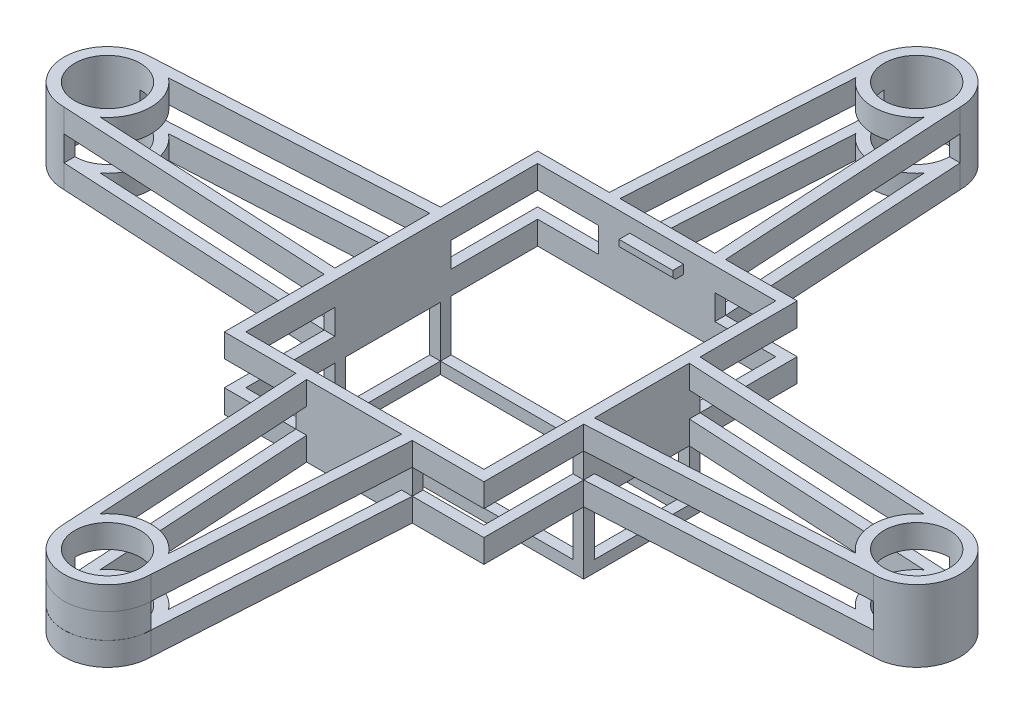
SolidWorks part; units mm, degrees
ref_plane "Front Plane" through (0, 0, 0) normal (0, 0, 1) x (1, 0, 0)
ref_plane "Top Plane" through (0, 0, 0) normal (0, 1, 0) x (1, 0, 0)
ref_plane "Right Plane" through (0, 0, 0) normal (1, 0, 0) x (0, 0, -1)
other "Center of Mass"
sketch "Sketch1" plane through (0, 0, 0) normal (0, 1, 0) x (1, 0, 0)
  line L0 (-15.0219, 23.4518) -> (-15.0219, 12.6018)
  line L1 (-13.8219, 22.2518) -> (12.7781, 22.2518)
  line L2 (-13.8219, 22.2518) -> (-13.8219, -10.3482)
  line L3 (-13.8219, -10.3482) -> (12.7781, -10.3482)
  line L4 (12.7781, 22.2518) -> (12.7781, -10.3482)
  line L5 (-15.0219, -11.5482) -> (-7.0219, -11.5482)
  line L6 (13.9781, 23.4518) -> (13.9781, 12.6018)
  line L7 (-15.0219, 23.4518) -> (-7.0219, 23.4518)
  line L8 (-0.5219, 23.4518) -> (-0.5219, 46.4518) construction
  line L9 (-5.3719, 51.3018) -> (-7.0219, 23.4518)
  line L10 (4.3281, 51.3018) -> (5.9781, 23.4518)
  line L11 (-4.3465, 48.3194) -> (-5.824, 23.3808)
  line L12 (3.3027, 48.3194) -> (4.7802, 23.3808)
  line L13 (-15.0219, 6.1018) -> (-40.8719, 6.1018) construction
  line L14 (4.3373, -39.0982) -> (5.9781, -11.5482)
  line L15 (3.31, -36.1101) -> (4.776, -11.5482)
  line L16 (-5.3719, -39.3982) -> (-7.0219, -11.5482)
  line L17 (-4.3538, -36.1101) -> (-5.8198, -11.5482)
  line L18 (-5.8198, 23.4518) -> (4.776, 23.4518)
  line L19 (-15.0219, 23.4518) -> (13.9781, 23.4518) construction
  line L20 (5.9781, 23.4518) -> (13.9781, 23.4518)
  line L21 (3.1302, 51.2308) -> (4.7802, 23.3808) construction
  line L22 (-4.174, 51.2308) -> (-5.824, 23.3808) construction
  line L23 (5.9781, -11.5482) -> (13.9781, -11.5482)
  line L24 (-15.0219, -11.5482) -> (13.9781, -11.5482) construction
  line L25 (-5.8198, -11.5482) -> (4.776, -11.5482)
  line L26 (-15.0219, 12.6018) -> (-45.7219, 10.9518)
  line L27 (-15.0219, -0.3982) -> (-45.7219, 1.2518)
  line L28 (-15.0219, 11.4001) -> (-42.7204, 9.9114)
  line L29 (-15.0219, 0.8035) -> (-42.7204, 2.2922)
  line L30 (-14.9575, 11.4035) -> (-45.6575, 9.7535) construction
  line L31 (-14.9575, 0.8001) -> (-45.6575, 2.4501) construction
  line L32 (-15.0219, 11.4001) -> (-15.0219, 0.8035)
  line L33 (-15.0219, 23.4518) -> (-15.0219, -11.5482) construction
  line L34 (-15.0219, -0.3982) -> (-15.0219, -11.5482)
  line L35 (-0.5219, 19.2522) -> (-0.5219, -5.3695) construction
  line L36 (13.9781, -0.3982) -> (44.6781, 1.2518)
  line L37 (13.9781, 0.8035) -> (41.6765, 2.2922)
  line L38 (13.9781, 12.6018) -> (44.6781, 10.9518)
  line L39 (13.9781, 11.4001) -> (41.6765, 9.9114)
  line L40 (13.9781, 11.4001) -> (13.9781, 0.8035)
  line L41 (13.9781, 23.4518) -> (13.9781, -11.5482) construction
  line L42 (13.9781, -0.3982) -> (13.9781, -11.5482)
  circle A0 centre (-0.5219, 51.3018) radius 3.65
  arc A1 (-4.3465, 48.3194) -> (3.3027, 48.3194) centre (-0.5219, 51.3018) ccw
  arc A2 (-4.3538, -36.1101) -> (3.31, -36.1101) centre (-0.5219, -39.0982) cw
  circle A3 centre (-0.5219, -39.0982) radius 3.65
  circle A4 centre (-0.5219, 51.3018) radius 4.85 construction
  arc A5 (4.3281, 51.3018) -> (-5.3719, 51.3018) centre (-0.5219, 51.3018) ccw
  arc A6 (4.3373, -39.0982) -> (-5.3719, -39.3982) centre (-0.5219, -39.0982) cw
  circle A7 centre (-45.7219, 6.1018) radius 3.65
  arc A8 (-45.7219, 10.9518) -> (-45.7219, 1.2518) centre (-45.7219, 6.1018) ccw
  circle A9 centre (-45.7219, 6.1018) radius 4.85 construction
  arc A10 (-42.7204, 2.2922) -> (-42.7204, 9.9114) centre (-45.7219, 6.1018) ccw
  arc A11 (41.6765, 2.2922) -> (41.6765, 9.9114) centre (44.6781, 6.1018) cw
  arc A12 (44.6781, 10.9518) -> (44.6781, 1.2518) centre (44.6781, 6.1018) cw
  circle A13 centre (44.6781, 6.1018) radius 3.65
  point P10 (-0.5219, 51.3018)
  point P15 (-7.0219, 23.4518)
  point P16 (5.9781, 23.4518)
  point P29 (-45.7219, 6.1018)
  point P39 (-0.5219, -39.0982)
  point P44 (-15.0219, 6.1018)
  point P49 (-15.0219, 12.6018)
  point P50 (-15.0219, -0.3982)
  point P76 (44.6781, 6.1018)
  dimension "D5" = 4.85
  dimension "D13" = 1.2
  dimension "D18" = 90.4
  dimension "D20" = 7.3
  dimension "D1" = 26.6
  dimension "D2" = 32.6
  dimension "D4" = 23
  dimension "D7" = 6.5
  dimension "D8" = 6.5
  dimension "D11" = 25.85
  dimension "D12" = 4.85
  dimension "D14" = 6.5
  dimension "D15" = 6.5
  dimension "D19" = 90.4
  dimension "D3" = 1.2
  dimension "D6" = 1.2
  dimension "D9" = 1.2
  dimension "D10" = 1.2
  dimension "D16" = 1.2
  dimension "D17" = 1.2
extrude "Boss-Extrude1" add sketch "Sketch1" along normal blind 8 contours A12 L38 L6 L20 L10 A5 L9 L7 L0 L26 A8 L27 L34 L5 L16 A6 L14 L23 L42 L36 L29 A10 L28 L32 A3 A2 L17 L25 L15 A0 L1 L4 L3 L2 L11 A1 L12 L18 A7 region at (-11.0219, 0, -23.3102)
sketch "Sketch2" plane through (0, 0, -22.2518) normal (0, 0, 1) x (1, 0, 0)
  line L0 (-13.8219, 8) -> (12.7781, 8) construction
  line L2 (-0.5219, 6.4) -> (-3.5219, 6.4)
  line L3 (-0.5219, 6.4) -> (-0.5219, 5.7)
  line L4 (-0.5219, 5.7) -> (-3.5219, 5.7)
  line L5 (-3.5219, 6.4) -> (-3.5219, 5.7)
  line L6 (-0.5219, 6.4) -> (2.4781, 6.4)
  line L7 (-0.5219, 6.4) -> (-0.5219, 5.7)
  line L8 (-0.5219, 5.7) -> (2.4781, 5.7)
  line L9 (2.4781, 6.4) -> (2.4781, 5.7)
  point P0 (-0.5219, 8)
  point P1 (-0.5219, 6.4)
  dimension "D1" = 1.6
  dimension "D2" = 0.7
  dimension "D3" = 3
  dimension "D4" = 3
extrude "Boss-Extrude2" add sketch "Sketch2" along normal blind 1.2 contours L2 L5 L4 L3 | L9 L6 L3 L8 region at (-2.0219, 6.05, -22.2518) region at (0.9781, 6.05, -22.2518)
sketch "Sketch3" plane through (0, 0, 10.3482) normal (0, 0, -1) x (-1, 0, 0)
  line L0 (13.8219, 8) -> (-12.7781, 8) construction
  line L2 (0.5219, 6.4) -> (-2.4781, 6.4)
  line L3 (0.5219, 6.4) -> (0.5219, 5.7)
  line L4 (0.5219, 5.7) -> (-2.4781, 5.7)
  line L5 (-2.4781, 6.4) -> (-2.4781, 5.7)
  line L6 (0.5219, 6.4) -> (3.5219, 6.4)
  line L7 (0.5219, 6.4) -> (0.5219, 5.7)
  line L8 (0.5219, 5.7) -> (3.5219, 5.7)
  line L9 (3.5219, 6.4) -> (3.5219, 5.7)
  point P0 (0.5219, 8)
  point P1 (0.5219, 6.4)
  dimension "D1" = 1.6
  dimension "D2" = 0.7
  dimension "D3" = 3
  dimension "D4" = 3
extrude "Boss-Extrude3" add sketch "Sketch3" along normal blind 1.2 contours L2 L5 L4 L3 | L9 L6 L3 L8 region at (0.9781, 6.05, 10.3482) region at (-2.0219, 6.05, 10.3482)
chamfer "Chamfer1" distance 1.2 angle 45 2 edges at (-0.5219, 5.7, -22.2518) (-0.5219, 5.7, 10.3482)
sketch "Sketch4" plane through (0, 0, -23.4518) normal (0, 0, -1) x (-1, 0, 0)
  line L0 (-49.5281, 4) -> (52.6578, 4) construction
  line L1 (-49.5281, 8) -> (-49.5281, 0) construction
  line L3 (52.6578, 4) -> (-53.577, 4)
  line L4 (52.6578, 4) -> (52.6578, 5.4)
  line L5 (52.6578, 5.4) -> (-53.577, 5.4)
  line L6 (-53.577, 4) -> (-53.577, 5.4)
  line L7 (-53.577, 4) -> (52.6578, 4)
  line L8 (-53.577, 4) -> (-53.577, 2.6)
  line L9 (-53.577, 2.6) -> (52.6578, 2.6)
  line L10 (52.6578, 4) -> (52.6578, 2.6)
  line M4 (5.8198, 0) -> (5.8198, 8)
  line M6 (-4.776, 8) -> (-4.776, 0)
  dimension "D1" = 1.4
  dimension "D2" = 1.4
extrude "Cut-Extrude1" cut sketch "Sketch4" against normal through all both and the other way through all contours L8 L9 L3 L7 M6 | L6 L7 L3 L5 M6 | L5 L3 M4 M6 | L9 L3 M6 M4 | L10 L3 L9 M4 | L4 L5 L3 M4 region at (-29.2388, 3.3, -23.4518) region at (-29.2388, 4.7, -23.4518) region at (-0.5219, 3.3, -23.4518) region at (-0.5219, 4.7, -23.4518) region at (29.1765, 3.3, -23.4518) region at (29.1765, 4.7, -23.4518)
sketch "Sketch5" plane through (0, 8, 0) normal (0, 1, 0) x (1, 0, 0)
  line L0 (-13.8219, 22.2518) -> (12.7781, 22.2518) construction
  line L1 (-7.0219, 23.4518) -> (5.9781, 23.4518)
  line L2 (-7.0219, 23.4518) -> (-7.0219, 22.2518)
  line L3 (-7.0219, 22.2518) -> (5.9781, 22.2518)
  line L4 (5.9781, 23.4518) -> (5.9781, 22.2518)
  line L5 (-13.8219, -10.3482) -> (12.7781, -10.3482) construction
  line L6 (-7.0219, -11.5482) -> (5.9781, -11.5482)
  line L7 (-7.0219, -11.5482) -> (-7.0219, -10.3482)
  line L8 (-7.0219, -10.3482) -> (5.9781, -10.3482)
  line L9 (5.9781, -11.5482) -> (5.9781, -10.3482)
  line L10 (-13.8219, 22.2518) -> (-13.8219, -10.3482) construction
  line L11 (-15.0219, 12.6018) -> (-13.8219, 12.6018)
  line L12 (-15.0219, 12.6018) -> (-15.0219, -0.3982)
  line L13 (-15.0219, -0.3982) -> (-13.8219, -0.3982)
  line L14 (-13.8219, 12.6018) -> (-13.8219, -0.3982)
  line L15 (12.7781, 22.2518) -> (12.7781, -10.3482) construction
  line L16 (13.9781, 12.6018) -> (12.7781, 12.6018)
  line L17 (13.9781, 12.6018) -> (13.9781, -0.3982)
  line L18 (13.9781, -0.3982) -> (12.7781, -0.3982)
  line L19 (12.7781, 12.6018) -> (12.7781, -0.3982)
extrude "Boss-Extrude4" add sketch "Sketch5" against normal through all
sketch "Sketch6" plane through (0, 8, 0) normal (0, 1, 0) x (1, 0, 0)
  line L0 (-5.3719, 51.3018) -> (-4.1719, 51.3018)
  line L1 (3.1281, 51.3018) -> (4.3281, 51.3018)
  line L2 (-10.3547, 6.1018) -> (10.8442, 6.1018) construction
  line L3 (3.1281, -39.0982) -> (4.3281, -39.0982)
  line L4 (-5.3719, -39.0982) -> (-4.1719, -39.0982)
  line L5 (44.6781, 9.7518) -> (44.6781, 10.9518)
  line L6 (44.6781, 1.2518) -> (44.6781, 2.4518)
  line L7 (-0.5219, 19.9558) -> (-0.5219, -2.6234) construction
  line L8 (-45.7219, 1.2518) -> (-45.7219, 2.4518)
  line L9 (-45.7219, 9.7518) -> (-45.7219, 10.9518)
  arc A0 (4.3281, 51.3018) -> (-5.3719, 51.3018) centre (-0.5219, 51.3018) ccw
  arc A1 (3.1281, 51.3018) -> (-4.1719, 51.3018) centre (-0.5219, 51.3018) ccw
  arc A2 (3.1281, -39.0982) -> (-4.1719, -39.0982) centre (-0.5219, -39.0982) cw
  arc A3 (4.3281, -39.0982) -> (-5.3719, -39.0982) centre (-0.5219, -39.0982) cw
  arc A4 (44.6781, 9.7518) -> (44.6781, 2.4518) centre (44.6781, 6.1018) cw
  arc A5 (44.6781, 10.9518) -> (44.6781, 1.2518) centre (44.6781, 6.1018) cw
  arc A6 (-45.7219, 10.9518) -> (-45.7219, 1.2518) centre (-45.7219, 6.1018) ccw
  arc A7 (-45.7219, 9.7518) -> (-45.7219, 2.4518) centre (-45.7219, 6.1018) ccw
  dimension "D2" = 7.3
extrude "Boss-Extrude5" add sketch "Sketch6" against normal through all
sketch "Sketch7" plane through (0, 0, 0) normal (0, -1, 0) x (1, 0, 0)
  line L0 (-13.8219, -22.2518) -> (-13.8219, 10.3482) construction
  line L1 (-15.0219, 0.3982) -> (-13.8219, 0.3982)
  line L2 (-15.0219, 0.3982) -> (-15.0219, -0.8039)
  line L3 (-15.0219, -0.8039) -> (-13.8219, -0.8039)
  line L4 (-13.8219, 0.3982) -> (-13.8219, -0.8039)
  line L5 (12.7781, -22.2518) -> (12.7781, 10.3482) construction
  line L6 (-15.0219, -11.4001) -> (-13.8219, -11.4001)
  line L7 (-15.0219, -11.4001) -> (-15.0219, -12.6018)
  line L8 (-15.0219, -12.6018) -> (-13.8219, -12.6018)
  line L9 (-13.8219, -11.4001) -> (-13.8219, -12.6018)
  line L10 (13.9781, 0.3982) -> (12.7781, 0.3982)
  line L11 (13.9781, 0.3982) -> (13.9781, -0.8039)
  line L12 (13.9781, -0.8039) -> (12.7781, -0.8039)
  line L13 (12.7781, 0.3982) -> (12.7781, -0.8039)
  line L15 (13.9781, -11.4001) -> (12.7781, -11.4001)
  line L16 (13.9781, -11.4001) -> (13.9781, -12.6018)
  line L17 (13.9781, -12.6018) -> (12.7781, -12.6018)
  line L18 (12.7781, -11.4001) -> (12.7781, -12.6018)
extrude "Boss-Extrude6" add sketch "Sketch7" along normal blind 7
sketch "Sketch8" plane through (-13.8219, 0, 0) normal (1, 0, 0) x (0, 0, -1)
  line L0 (0.8039, -7) -> (0.8039, 0) construction
  line L1 (-0.3982, -7) -> (0.8039, -7)
  line L2 (-0.3982, -7) -> (-0.3982, -5.7)
  line L3 (-0.3982, -5.7) -> (0.8039, -5.7)
  line L4 (0.8039, -7) -> (0.8039, -5.7)
  line L5 (11.4001, -7) -> (11.4001, 0) construction
  line L6 (11.4001, -5.7) -> (12.6018, -5.7)
  line L7 (11.4001, -5.7) -> (11.4001, -7)
  line L8 (11.4001, -7) -> (12.6018, -7)
  line L9 (12.6018, -5.7) -> (12.6018, -7)
  dimension "D1" = 1.3
extrude "Boss-Extrude7" add sketch "Sketch8" along normal up to surface (26.6 mm away) up to face at (12.7781, 1, -6.0418)
sketch "Sketch9" plane through (0, 0, -12.6018) normal (0, 0, -1) x (-1, 0, 0)
  line L1 (-13.9781, -7) -> (-12.7781, -7)
  line L2 (-13.9781, -7) -> (-13.9781, -5.7)
  line L3 (-13.9781, -5.7) -> (-12.7781, -5.7)
  line L4 (-12.7781, -7) -> (-12.7781, -5.7)
  line L5 (15.0219, -7) -> (13.8219, -7)
  line L6 (15.0219, -7) -> (15.0219, -5.7)
  line L7 (15.0219, -5.7) -> (13.8219, -5.7)
  line L8 (13.8219, -7) -> (13.8219, -5.7)
extrude "Boss-Extrude8" add sketch "Sketch9" against normal up to surface (11.7979 mm away) up to face at (-0.5219, -3.175, -0.8039)
